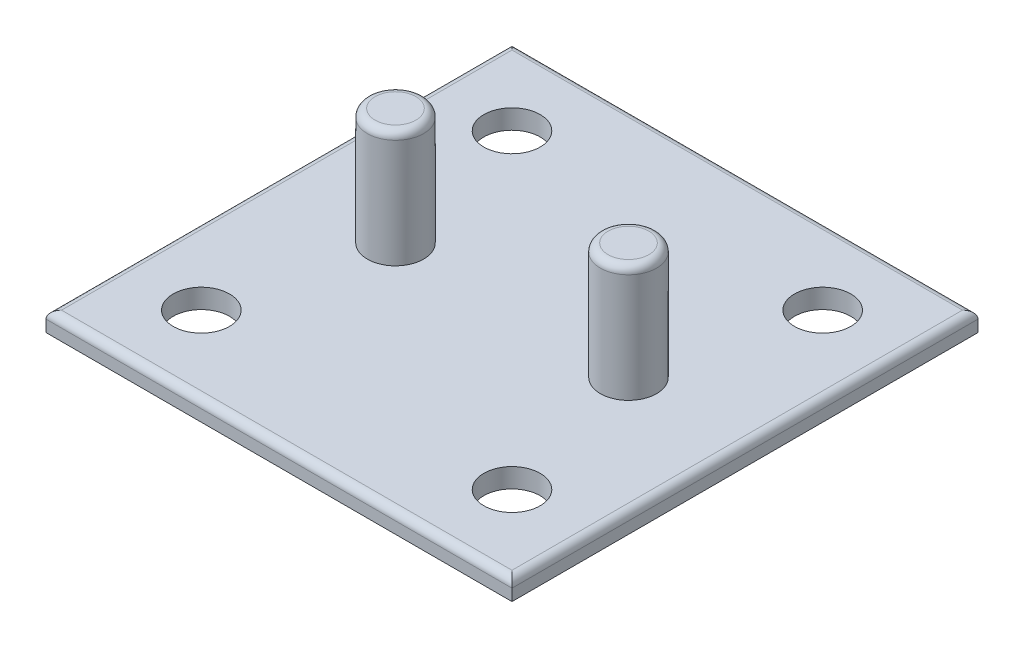
SolidWorks part; units mm, degrees
ref_plane "Plan de face" through (0, 0, 0) normal (0, 0, 1) x (1, 0, 0)
ref_plane "Plan de dessus" through (0, 0, 0) normal (0, 1, 0) x (1, 0, 0)
ref_plane "Plan de droite" through (0, 0, 0) normal (1, 0, 0) x (0, 0, -1)
sketch "Esquisse3" plane through (0, 0, 0) normal (0, 1, 0) x (1, 0, 0)
  line L1 (60, 60) -> (-60, 60)
  line L2 (60, 60) -> (60, -60)
  line L3 (60, -60) -> (-60, -60)
  line L4 (-60, 60) -> (-60, -60)
  line L5 (60, 60) -> (-60, -60) construction
  line L6 (60, -60) -> (-60, 60) construction
  point P0 (0, 0)
  dimension "D1" = 120
  dimension "D2" = 120
extrude "Boss.-Extru.2" add sketch "Esquisse3" along normal blind 5
sketch "Esquisse5" plane through (0, 5, 0) normal (0, 1, 0) x (1, 0, 0)
  line L0 (60, 60) -> (-60, 60) construction
  line L1 (-60, 60) -> (-60, -60) construction
  circle A0 centre (-40, 40) radius 7.25
  dimension "D1" = 14.5
  dimension "D2" = 20
  dimension "D3" = 20
extrude "Enlèv. mat.-Extru.1" cut sketch "Esquisse5" against normal blind 5
sketch "Esquisse6" plane through (0, 0, 0) normal (0, 1, 0) x (1, 0, 0)
  line L0 (-1000, 0) -> (49000, 0) construction
  line L1 (0, -1000) -> (0, 49000) construction
  circle A1 centre (-40, 40) radius 7.25 construction
  circle A2 centre (-40, 40) radius 7.25
  circle A3 centre (40, 40) radius 7.25
  circle A4 centre (-40, -40) radius 7.25
  circle A5 centre (40, -40) radius 7.25
extrude "Enlèv. mat.-Extru.7" cut sketch "Esquisse6" along normal blind 5
sketch "Esquisse11" plane through (0, 5, 0) normal (0, 1, 0) x (1, 0, 0)
  circle A0 centre (-30, 0) radius 7.25
  dimension "D1" = 30
  dimension "D2" = 14.5
extrude "Boss.-Extru.4" add sketch "Esquisse11" along normal blind 30
sketch "Esquisse14" plane through (0, 5, 0) normal (0, 1, 0) x (1, 0, 0)
  line L0 (0, -1000) -> (0, 49000) construction
  circle A0 centre (30, 0) radius 7.25
  circle A1 centre (-30, 0) radius 7.25
  circle A2 centre (-30, 0) radius 7.25
  dimension "D1" = 0
extrude "Boss.-Extru.6" add sketch "Esquisse14" along normal blind 30
fillet "Congé2" radius 2 1 edges at (30, 35, -7.25)
fillet "Congé3" radius 2 1 edges at (-30, 35, 7.25)
fillet "Congé4" radius 2 4 edges at (60, 5, 0) (0, 5, -60) (-60, 5, 0) (0, 5, 60)
